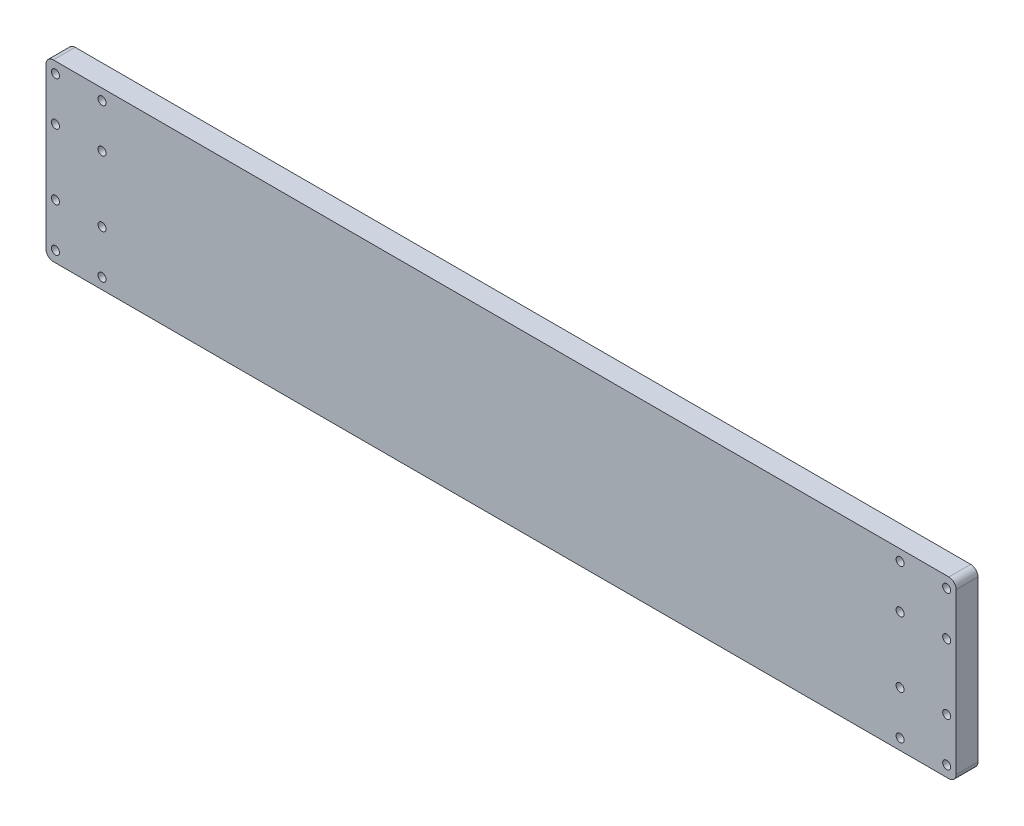
SolidWorks part; units mm, degrees
ref_plane "Plan de face" through (0, 0, 0) normal (0, 0, 1) x (1, 0, 0)
ref_plane "Plan de dessus" through (0, 0, 0) normal (0, 1, 0) x (1, 0, 0)
ref_plane "Plan de droite" through (0, 0, 0) normal (1, 0, 0) x (0, 0, -1)
sketch "Esquisse1" plane through (0, 0, 0) normal (0, 0, 1) x (1, 0, 0)
  line L1 (0, 0) -> (625, 0)
  line L2 (0, 0) -> (0, 120)
  line L3 (0, 120) -> (625, 120)
  line L4 (625, 0) -> (625, 120)
  dimension "D1" = 120
  dimension "D2" = 625
extrude "Boss.-Extru.1" add sketch "Esquisse1" along normal blind 15
sketch "Esquisse2" plane through (0, 0, 15) normal (0, 0, 1) x (1, 0, 0)
  line L0 (312.5, 0) -> (312.5, 120) construction
  line L1 (0, 0) -> (625, 0) construction
  line L2 (625, 120) -> (0, 120) construction
  line L3 (22.5, 120) -> (22.5, 0) construction
  line L4 (22.5, 60) -> (0, 60) construction
  line L5 (0, 120) -> (0, 0) construction
  line L6 (6.5, 112.5) -> (6.5, 82.5) construction
  line L7 (618.5, 112.5) -> (618.5, 82.5) construction
  line L8 (602.5, 60) -> (625, 60) construction
  line L9 (602.5, 120) -> (602.5, 0) construction
  circle A0 centre (6.5, 112.5) radius 2.75
  circle A1 centre (6.5, 82.5) radius 2.75
  circle A2 centre (38.5, 82.5) radius 2.75
  circle A3 centre (38.5, 112.5) radius 2.75
  circle A4 centre (38.5, 7.5) radius 2.75
  circle A5 centre (38.5, 37.5) radius 2.75
  circle A6 centre (6.5, 37.5) radius 2.75
  circle A7 centre (6.5, 7.5) radius 2.75
  circle A8 centre (618.5, 7.5) radius 2.75
  circle A9 centre (618.5, 37.5) radius 2.75
  circle A10 centre (586.5, 37.5) radius 2.75
  circle A11 centre (586.5, 7.5) radius 2.75
  circle A12 centre (586.5, 112.5) radius 2.75
  circle A13 centre (586.5, 82.5) radius 2.75
  circle A14 centre (618.5, 82.5) radius 2.75
  circle A15 centre (618.5, 112.5) radius 2.75
  dimension "D1" = 30
  dimension "D2" = 32
  dimension "D3" = 5.5
  dimension "D4" = 45
  dimension "D5" = 580
extrude "Enlèv. mat.-Extru.1" cut sketch "Esquisse2" against normal through all both and the other way through all
fillet "Congé1" radius 5 4 edges at (625, 120, 7.5) (625, 0, 7.5) (0, 0, 7.5) (0, 120, 7.5)
